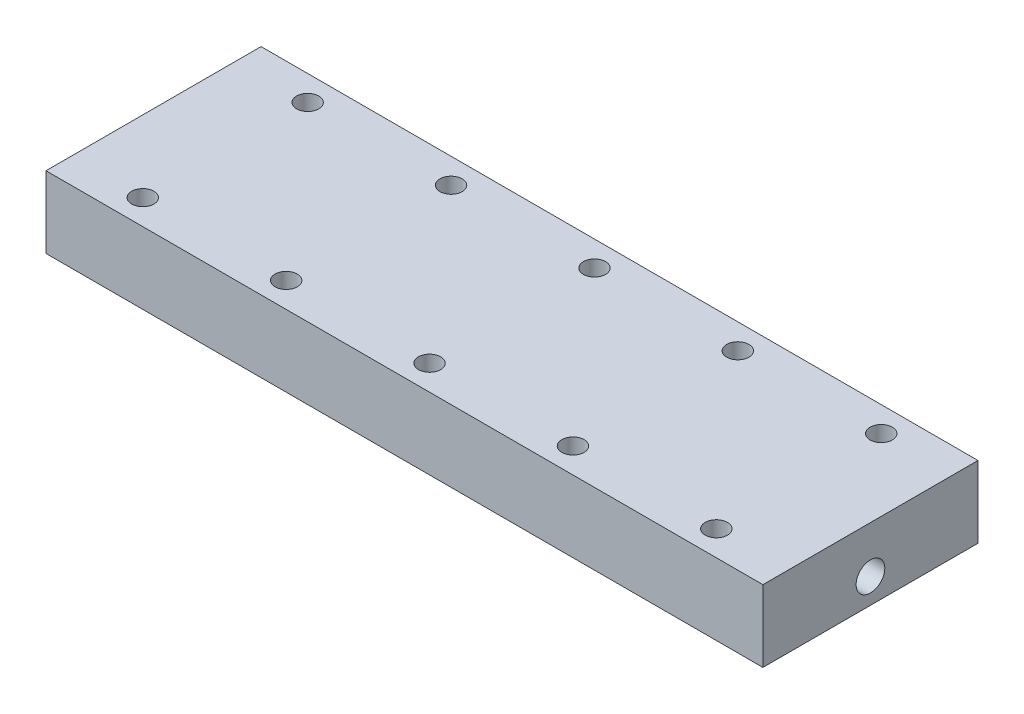
SolidWorks part; units mm, degrees
ref_plane "Front Plane" through (0, 0, 0) normal (0, 0, 1) x (1, 0, 0)
ref_plane "Top Plane" through (0, 0, 0) normal (0, 1, 0) x (1, 0, 0)
ref_plane "Right Plane" through (0, 0, 0) normal (1, 0, 0) x (0, 0, -1)
sketch "Sketch1" plane through (0, 0, 0) normal (0, 1, 0) x (1, 0, 0)
  line L0 (-50, 0) -> (50, 0)
  line L1 (50, 0) -> (50, 30)
  line L2 (50, 30) -> (-50, 30)
  line L3 (-50, 30) -> (-50, 0)
  dimension "D1" = 100
  dimension "D2" = 50
  dimension "D3" = 30
  dimension "D4" = 30
extrude "Boss-Extrude1" add sketch "Sketch1" along normal blind 10
sketch "Sketch2" plane through (0, 0, 0) normal (0, 1, 0) x (1, 0, 0)
  line L0 (45, 24) -> (45, 6)
  line L1 (45, 6) -> (15, 6)
  line L2 (15, 6) -> (15, 24)
  line L3 (15, 24) -> (45, 24)
  line L4 (-50, 0) -> (50, 0) construction
  line L6 (50, 0) -> (50, 30) construction
  dimension "D1" = 18
  dimension "D2" = 6
  dimension "D3" = 30
  dimension "D4" = 5
extrude "Cut-Extrude1" cut sketch "Sketch2" against normal blind 8.5 and the other way blind 8.5
sketch "Sketch4" plane through (0, 0, 0) normal (0, 1, 0) x (1, 0, 0)
  line L0 (15, 6) -> (25, 6)
  line L1 (45, 6) -> (15, 6) construction
  line L2 (25, 6) -> (25, 24)
  line L3 (15, 24) -> (45, 24) construction
  line L4 (25, 24) -> (15, 24)
  line L5 (15, 24) -> (15, 6)
  dimension "D1" = 10
extrude "Boss-Extrude2" add sketch "Sketch4" along normal blind 10
sketch "Sketch3" plane through (0, 0, 0) normal (0, 1, 0) x (1, 0, 0)
  line L0 (50, 15) -> (-50, 15) construction
  line L1 (50, 0) -> (50, 30) construction
  line L2 (-50, 30) -> (-50, 0) construction
  line L3 (-45, 15) -> (-45, 8.41)
  line L4 (-45, 8.41) -> (35, 6.89)
  line L5 (35, 6.89) -> (35, 15)
  line L6 (35, 15) -> (-45, 15)
  line L8 (25, 6) -> (25, 24) construction
  dimension "D1" = 80
  dimension "D3" = 8.11
  dimension "D4" = 6.59
  dimension "D5" = 10
revolve "Cut-Revolve1" cut sketch "Sketch3" angle 360 about L0
sketch "Sketch6" plane through (0, 0, 0) normal (0, 1, 0) x (1, 0, 0)
  line L0 (-50, 15) -> (47.3429, 15) construction
  line L1 (-50, 30) -> (-50, 0) construction
  line L2 (25, 22.92) -> (25, 20.42)
  line L3 (25, 20.42) -> (15.0477, 20.23)
  line L4 (15.0477, 20.23) -> (15, 22.73)
  line L5 (-45, 21.59) -> (25, 22.92) construction
  line L6 (15, 22.73) -> (25, 22.92)
  dimension "D1" = 10
  dimension "D2" = 2.5
  dimension "D3" = 2.5
revolve "Revolve1" add sketch "Sketch6" angle 180 about L0
sketch "Sketch7" plane through (0, 0, 0) normal (0, 1, 0) x (1, 0, 0)
  line L0 (-45, 15) -> (38.1554, 15) construction
  line L1 (-45, 8.41) -> (-45, 21.59) construction
  line L2 (-35, 21.78) -> (-22.5, 22.0175)
  line L3 (-45, 21.59) -> (15, 22.73) construction
  line L4 (-22.5, 22.0175) -> (-22.5, 19.5175)
  line L5 (-22.5, 19.5175) -> (-35, 19.28)
  line L6 (-35, 19.28) -> (-35, 21.78)
  dimension "D1" = 2.5
  dimension "D2" = 2.5
  dimension "D3" = 12.5
  dimension "D4" = 10
revolve "Revolve2" add sketch "Sketch7" angle 180 about L0
sketch "Sketch8" plane through (0, 0, 0) normal (0, 1, 0) x (1, 0, 0)
  line L0 (-45, 15) -> (32.5702, 15) construction
  line L1 (-45, 8.41) -> (-45, 21.59) construction
  line L2 (-10, 22.255) -> (-10, 19.755)
  line L3 (-22.5, 22.0175) -> (15, 22.73) construction
  line L4 (-10, 19.755) -> (2.5, 19.9925)
  line L5 (2.5, 19.9925) -> (2.5, 22.4925)
  line L6 (2.5, 22.4925) -> (-10, 22.255)
  dimension "D1" = 12.5
  dimension "D2" = 2.5
  dimension "D3" = 2.5
  dimension "D4" = 12.5
revolve "Revolve3" add sketch "Sketch8" angle 180 about L0
ref_plane "Plane1" through (-50, 0, 0) normal (-1, 0, 0) x (0, 0, 1)
sketch "Sketch9" plane through (-50, 0, 0) normal (-1, 0, 0) x (0, 0, 1)
  line L0 (0, 10) -> (0, 0) construction
  line L1 (-30, 0) -> (0, 0) construction
  circle A0 centre (-15, 3.5) radius 1
  dimension "D2" = 2
  dimension "D1" = 15
  dimension "D3" = 3.5
extrude "Cut-Extrude2" cut sketch "Sketch9" against normal blind 12
ref_plane "Plane2" through (50, 0, 0) normal (1, 0, 0) x (0, 0, -1)
sketch "Sketch10" plane through (50, 0, 0) normal (1, 0, 0) x (0, 0, -1)
  circle A0 centre (15, 3.5) radius 2
  dimension "D1" = 4
extrude "Cut-Extrude3" cut sketch "Sketch10" against normal blind 12
fillet "Fillet3" radius 1.2 10 edges at (15.0477, 5.23, -15) (15, 7.73, -15) (-10, 7.255, -15) (2.5, 7.4925, -15) (2.5, 4.9925, -15) (-10, 4.755, -15) (-22.5, 7.0175, -15) (-22.5, 4.5175, -15) (-35, 6.78, -15) (-35, 4.28, -15)
fillet "Fillet5" radius 1.25 1 edges at (25, 5.42, -15)
fillet "Fillet7" radius 2 8 edges at (25, 4.25, -24) (25, 4.25, -6) (45, 4.25, -24) (35, 8.5, -24) (45, 4.25, -6) (45, 8.5, -15) (35, 8.5, -6) (25, 8.5, -15)
sketch "Sketch11" plane through (0, 0, 0) normal (0, 1, 0) x (1, 0, 0)
  line L0 (-50, 8.25) -> (-50, -8.25) construction
  line L2 (-50, 0) -> (50, 0) construction
  line L3 (-50, 0) -> (50, 0) construction
  line L4 (50, 30) -> (-50, 30) construction
  line L5 (-50, 30) -> (-50, 0) construction
  circle A0 centre (-40, 3.5) radius 1.55
  circle A1 centre (-20, 3.5) radius 1.55
  circle A2 centre (0, 3.5) radius 1.55
  circle A3 centre (20, 3.5) radius 1.55
  circle A4 centre (40, 3.5) radius 1.55
  circle A5 centre (-40, 26.5) radius 1.55
  circle A6 centre (-20, 26.5) radius 1.55
  circle A7 centre (0, 26.5) radius 1.55
  circle A8 centre (20, 26.5) radius 1.55
  circle A9 centre (40, 26.5) radius 1.55
  dimension "D11" = 3.1
  dimension "D12" = 3.1
  dimension "D13" = 3.1
  dimension "D14" = 3.1
  dimension "D15" = 3.1
  dimension "D17" = 3.1
  dimension "D18" = 3.1
  dimension "D21" = 3.1
  dimension "D23" = 3.1
  dimension "D25" = 3.1
  dimension "D1" = 10
  dimension "D2" = 20
  dimension "D3" = 20
  dimension "D4" = 20
  dimension "D5" = 20
  dimension "D6" = 3.5
  dimension "D7" = 3.5
  dimension "D8" = 3.5
  dimension "D9" = 3.5
  dimension "D10" = 3.5
  dimension "D16" = 3.5
  dimension "D19" = 3.5
  dimension "D20" = 3.5
  dimension "D22" = 3.5
  dimension "D24" = 3.5
  dimension "D26" = 10
  dimension "D27" = 20
  dimension "D28" = 20
  dimension "D29" = 20
  dimension "D30" = 20
extrude "Cut-Extrude4" cut sketch "Sketch11" against normal blind 20 and the other way blind 20
